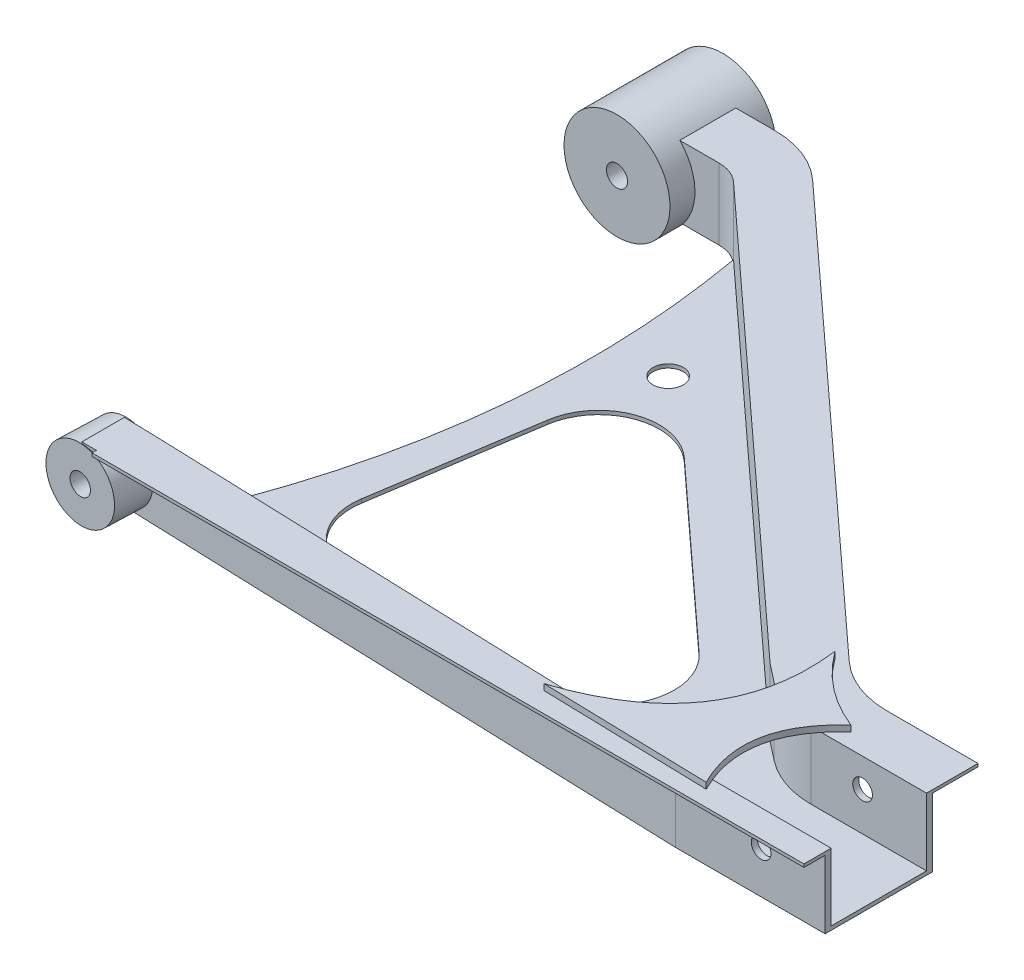
SolidWorks part; units mm, degrees
ref_plane "前视基准面" through (0, 0, 0) normal (0, 0, 1) x (1, 0, 0)
ref_plane "上视基准面" through (0, 0, 0) normal (0, 1, 0) x (1, 0, 0)
ref_plane "右视基准面" through (0, 0, 0) normal (1, 0, 0) x (0, 0, -1)
sketch "草图2" plane through (0, 0, 0) normal (0, 1, 0) x (1, 0, 0)
  line L0 (0, 0) -> (480.0188, 0)
  line L1 (480.0188, 0) -> (480.0188, 115)
  line L2 (480.0188, 115) -> (419.7021, 115)
  line L3 (379.1744, 130.7563) -> (354.1823, 103.4726)
  line L4 (0, 410) -> (50, 410)
  line L5 (0, 410) -> (50.9997, 410)
  line L6 (91.5274, 394.2437) -> (379.1744, 130.7563)
  line L7 (0, 410) -> (0, 373)
  line L8 (0, 373) -> (50.9997, 373)
  line L9 (37, 373) -> (50.9997, 373)
  line L10 (66.5353, 366.9601) -> (354.1823, 103.4726)
  line L11 (480.0188, 115) -> (480.0188, 81)
  line L12 (66.5353, 366.9601) -> (381.9906, 78) construction
  line L13 (480.0188, 115) -> (396.3754, 115) construction
  line L14 (91.5274, 394.2437) -> (396.3754, 115) construction
  line L15 (37, 37) -> (37, 373) construction
  line L16 (37, 37) -> (443.0188, 37) construction
  line L17 (443.0188, 37) -> (443.0188, 78) construction
  line L18 (443.0188, 78) -> (381.9906, 78) construction
  line L19 (0, 0) -> (0, 410) construction
  line L20 (480.0188, 81) -> (403.5965, 81)
  line L21 (354.1823, 103.4726) -> (366.6401, 93.7324)
  line L22 (480.0188, 81) -> (480.0188, 18)
  line L23 (0, 0) -> (0, 31.0268)
  line L24 (25.4913, 30.335) -> (381.0638, 18)
  line L25 (0, 31.0268) -> (25.4913, 30.335)
  line L26 (265.8438, 143.7079) -> (280.2673, 130.4958)
  line L27 (96.9207, 214.0677) -> (80.4577, 107.0837)
  line L28 (210.4849, 194.4171) -> (280.2673, 130.4958)
  line L29 (119.9923, 61) -> (253.2488, 61)
  line L30 (167.2957, 61) -> (119.9923, 61)
  line L31 (119.9923, 61) -> (253.2488, 61)
  line L32 (163.4738, 237.4798) -> (280.2673, 130.4958)
  line L33 (46.2715, 344.8382) -> (333.9185, 81.3508) construction
  line L34 (25.3526, 26.3374) -> (380.9944, 14)
  line L35 (68.0904, 370.9601) -> (356.8842, 106.4222)
  line L36 (480.0188, 14) -> (380.9944, 14)
  line L37 (480.0188, 85) -> (403.5965, 85)
  line L38 (356.6461, 106.6238) -> (369.1039, 96.8836)
  line L39 (69.2372, 369.9097) -> (356.8842, 106.4222) construction
  line L40 (4, 377) -> (52.5548, 377)
  line L41 (4, 377) -> (50.9997, 377) construction
  line L42 (88.8623, 351.9328) -> (69.2372, 369.9097)
  line L43 (88.8623, 351.9328) -> (69.2372, 369.9097)
  line L44 (4, 377) -> (0, 377)
  line L45 (68.0904, 370.9601) -> (88.8623, 351.9328)
  line L46 (52.5548, 377) -> (4, 377)
  line L47 (480.0188, 81) -> (480.0188, 18)
  line L48 (25.3526, 26.3374) -> (0, 27.2169)
  line L49 (4, 410) -> (4, 377) construction
  line L50 (480.0188, 81) -> (480.0188, 18)
  line L51 (480.0188, 18) -> (381.0638, 18)
  line L52 (480.0188, 13.9985) -> (381.0638, 13.9985)
  line L54 (298.0704, 22.9377) -> (298.0704, 18.9363)
  arc A0 (91.5274, 394.2437) -> (50.9997, 410) centre (50.9997, 350) ccw
  arc A1 (66.5353, 366.9601) -> (50.9997, 373) centre (50.9997, 350) ccw
  arc A2 (403.5965, 81) -> (366.6401, 93.7324) centre (403.5965, 141) cw
  arc A3 (419.7021, 115) -> (379.1744, 130.7563) centre (419.7021, 175) cw
  arc A4 (96.9207, 214.0677) -> (163.4738, 237.4798) centre (136.4553, 207.984) cw
  arc A5 (253.2488, 61) -> (280.2673, 130.4958) centre (253.2488, 101) ccw
  arc A6 (119.9923, 61) -> (80.4577, 107.0837) centre (119.9923, 101) cw
  circle A7 centre (111.5668, 278.734) radius 10
  circle A8 centre (63.069, 52.1662) radius 10
  circle A9 centre (323.1518, 73.8233) radius 10
  arc A10 (403.5965, 85) -> (369.1039, 96.8836) centre (403.5965, 141) cw
  arc A11 (68.0904, 370.9601) -> (52.5548, 377) centre (52.5548, 354) ccw
  arc A12 (68.0904, 370.9601) -> (52.5548, 377) centre (52.5548, 354) ccw
  spline S0 degree 2 poles (66.5353, 366.9601) (97.4332, 191.9064) (25.4913, 30.335) knots 0 0 0 1 1 1
  dimension "D1" = 60
  dimension "D3" = 60
  dimension "D4" = 60
  dimension "D8" = 40
  dimension "D10" = 40
  dimension "D11" = 40
  dimension "D12" = 4
  dimension "D16" = 23
  dimension "D2" = 37
  dimension "D5" = 115
  dimension "D6" = 34
  dimension "D7" = 410
  dimension "D9" = 30
  dimension "D17" = 63
  dimension "D13" = 4
  dimension "D14" = 4
  dimension "D15" = 4
extrude "凸台-拉伸2" add sketch "草图2" along normal blind 2.5 contours L10 S0 L1 L20 A2 L21 L29 A6 L27 A4 L32 L28 L26 A5 A7 A8 A9 region at (77.4394, 0, -194.8129)
extrude "凸台-拉伸3" add sketch "草图2<4>" along normal blind 47 contours L35 A11 L40 L44 L7 L8 A1 L10 L3 | L37 A10 L38 L3 L21 A2 L20 L1 | L1 L51 L24 L25 L23 L48 L34 L36 region at (240.2819, 0, -21.2345) region at (59.4969, 0, -371.856) region at (441.8077, 0, -82.2838)
sketch "草图2<4>" plane through (0, 0, 0) normal (0, 1, 0) x (1, 0, 0) same geometry as "草图2"
extrude "凸台-拉伸4" add sketch "草图2<6>" along normal blind 47 contours A11 L35 L38 L3 L6 A0 L5 L4 L7 L44 L40 | A10 L37 L11 L2 A3 L3 L38 | L1 L51 L24 L25 L23 L48 L34 L36 | L34 L48 L23 L0 L1 L36 region at (209.2087, 0, -10.1086) region at (240.2819, 0, -21.2345) region at (420.5993, 0, -102.3702) region at (192.1226, 0, -275.3576)
sketch "草图2<6>" plane through (0, 0, 0) normal (0, 1, 0) x (1, 0, 0) same geometry as "草图2"
extrude "切除-拉伸2" cut sketch "草图2<8>" along normal blind 45 contours L23 L0 L1 | A10 L37 L11 L2 A3 L3 L38 | A11 L35 L38 L3 L6 A0 L5 L4 L7 L44 L40 region at (209.2087, 0, -10.1086) region at (420.5993, 0, -102.3702) region at (192.1226, 0, -275.3576)
sketch "草图2<8>" plane through (0, 0, 0) normal (0, 1, 0) x (1, 0, 0) same geometry as "草图2"
sketch "草图3" plane through (0, 47, 0) normal (0, 1, 0) x (1, 0, 0)
  line L0 (480.0188, 81) -> (420, 81)
  line L1 (480.0188, 81) -> (403.5965, 81) construction
  line L4 (405.0187, 10.4343) -> (295.0561, 13.3029)
  spline S0 degree 2 poles (420, 91) (390.9072, 102.6655) (372.5805, 128.0607) knots 0 0 0 1 1 1
  spline S1 degree 2 poles (420, 91) (381.9205, 56.3068) (405.0187, 10.4343) knots 0 0 0 1 1 1
  spline S2 degree 2 poles (372.5805, 128.0607) (383.5455, 42.3388) (295.0561, 13.3029) knots 0 0 0 1 1 1
  arc M10 (366.6401, 93.7324) -> (403.5965, 81) centre (403.5965, 141) ccw
  line M11 (403.5965, 81) -> (480.0188, 81)
extrude "凸台-拉伸5" add sketch "草图3" along normal blind 4 contours S2 L4 S1 M10 M11 | S0 S2 S1 M10 M11 region at (369.1996, 47, -40.6108) region at (390.6186, 47, -96.8295)
ref_plane "基准面2" through (0, 0, -377) normal (0, 0, -1) x (-1, 0, 0)
sketch "草图5" plane through (0, 0, -377) normal (0, 0, -1) x (-1, 0, 0)
  line L0 (0, 0) -> (0, 45)
  circle A0 centre (0, 22.5) radius 7
  circle A1 centre (0, 22.5) radius 35
extrude "凸台-拉伸6" add sketch "草图5" along normal blind 49.5 and the other way blind 20.5 contours A1 A0 region at (34.0101, 22.5, -377)
sketch "草图6" plane through (0.943, 0, -27.1842) normal (-0.0347, 0, 0.9994) x (0.9994, 0, 0.0347)
  line L0 (-0.9436, 45) -> (-0.9436, 0)
  line L1 (-0.9436, 22.5) -> (424.0564, 22.5)
  circle A0 centre (424.0564, 22.5) radius 13
  circle A1 centre (-0.9436, 22.5) radius 7
  circle A2 centre (-0.9436, 22.5) radius 23.5
  line M1 (-0.9436, 0) -> (380.28, 0)
  line M3 (380.28, 45) -> (-0.9436, 45)
  line M4 (-0.9436, 45) -> (-0.9436, 0)
extrude "凸台-拉伸8" add sketch "草图6<3>" along normal blind 24.5 and the other way blind 5.5 contours A2 A1 M3 M1 M4 | A2 A1 M3 M4 | A2 A1 M1 M4 region at (10.7433, 33.0132, -26.8442) region at (-10.4992, 22.5, -27.5811) region at (10.7433, 11.9868, -26.8442)
sketch "草图6<3>" plane through (0.943, 0, -27.1842) normal (-0.0347, 0, 0.9994) x (0.9994, 0, 0.0347) same geometry as "草图6"
extrude "切除-拉伸4" cut sketch "草图6" against normal blind 24.5 and the other way blind 35.5 contours L0 A1 | L0 A1 | A1 L0 region at (2.9691, 25.4709, -27.1139) region at (-2.9691, 22.5, -27.3199) region at (2.9691, 19.5291, -27.1139)
sketch "草图7" plane through (0.943, 0, -27.1842) normal (-0.0347, 0, 0.9994) x (0.9994, 0, 0.0347)
  line L0 (380.28, 22.5) -> (330.891, 22.5)
  line L1 (380.28, 45) -> (380.28, 0) construction
sketch "草图10" plane through (0, 0, -85) normal (0, 0, -1) x (-1, 0, 0)
  line L0 (-480.0188, 45) -> (-480.0188, 22.5)
  line L1 (-480.0188, 45) -> (-480.0188, 0) construction
  line L2 (-437.7488, 28) -> (-437.7488, 0)
  line L3 (-480.0188, 0) -> (-403.5965, 0) construction
  circle A1 centre (-437.7488, 28) radius 6.5
  dimension "D1" = 28
extrude "切除-拉伸5" cut sketch "草图10" against normal blind 118 and the other way blind 31 contours A1 region at (433.2826, 23.5338, -85)
sketch "草图12" plane through (0, 47, 0) normal (0, 1, 0) x (1, 0, 0)
  line L0 (0, 0) -> (9.6088, 0)
  line L1 (0, 0) -> (480.0188, 0) construction
  line L2 (9.6088, 0) -> (9.6088, 2.5115)
  line L3 (9.6088, 2.9115) -> (5, 2.9115)
  line L4 (0, 0) -> (0, 31.0268) construction
  line L5 (0, 2.3) -> (0, 0)
  line L6 (9.6088, 2.9115) -> (9.6088, 2.5115)
  line L7 (0, 2.3) -> (0, 2.9115)
  line L8 (0, 2.9115) -> (5, 2.9115)
extrude "切除-拉伸7" cut sketch "草图12" against normal blind 10
sketch "草图13" plane through (0.0936, 0, -2.6989) normal (-0.0347, 0, 0.9994) x (0.9994, 0, 0.0347)
  circle A0 centre (-0.9436, 22.5) radius 7
  circle A1 centre (-0.9436, 22.5) radius 23.5
extrude "凸台-拉伸9" add sketch "草图13" against normal blind 5
sketch "草图14" plane through (0, 0, -426.5) normal (0, 0, -1) x (-1, 0, 0)
  circle A0 centre (0, 22.5) radius 7
extrude "切除-拉伸8" cut sketch "草图14" against normal blind 326
